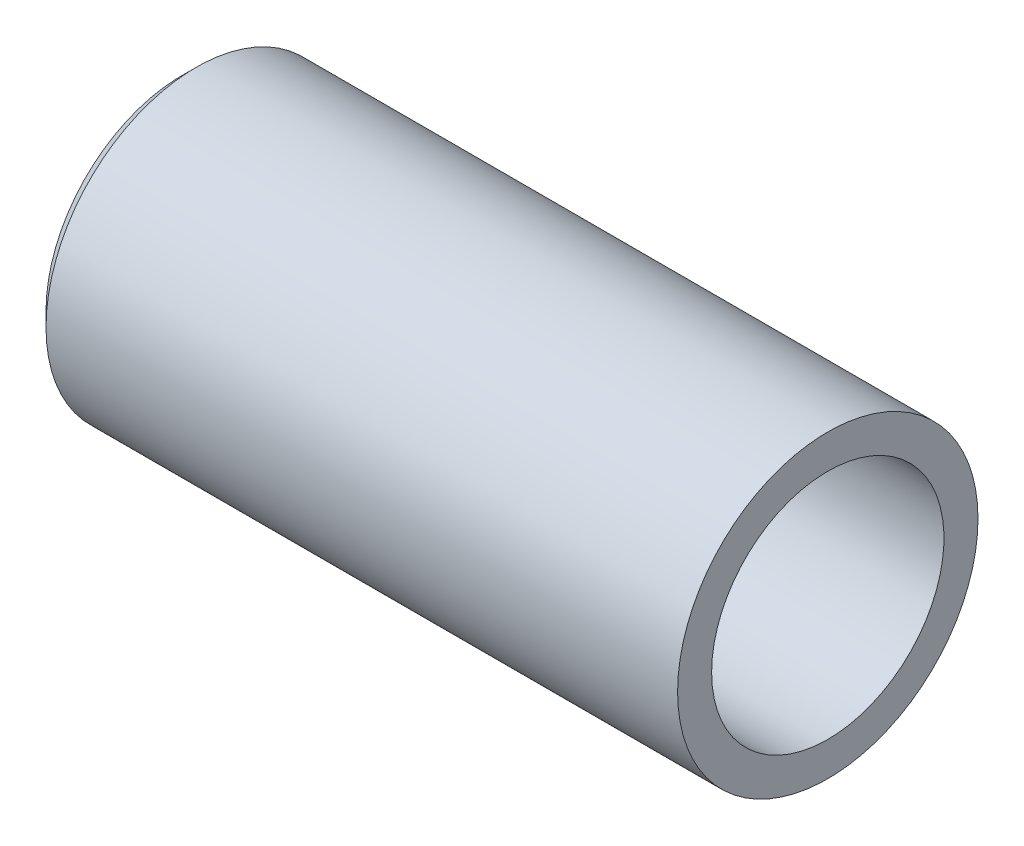
SolidWorks part; units mm, degrees
material "6061-T6 (SS)"
ref_plane "Front Plane" through (0, 0, 0) normal (0, 0, 1) x (1, 0, 0)
ref_plane "Top Plane" through (0, 0, 0) normal (0, 1, 0) x (1, 0, 0)
ref_plane "Right Plane" through (0, 0, 0) normal (1, 0, 0) x (0, 0, -1)
sketch "Sketch1" plane through (0, 0, 0) normal (0, 0, 1) x (1, 0, 0)
  line L0 (0, 0) -> (22.1407, 0) construction
  line L1 (0.8502, 5.2957) -> (23.1179, 5.2957)
  line L3 (0.3531, 4.0957) -> (23.1179, 4.0958)
  line L4 (23.3719, 5.2957) -> (23.3719, 1.3364) construction
  line L5 (23.1179, 5.2957) -> (23.1179, 4.0958)
  line L8 (0.3531, 4.0957) -> (0.3531, 4.7987)
  line L9 (0.3531, 4.7987) -> (0.8502, 5.2957)
  line L15 (0.3531, -7.9375) -> (0.3531, 7.9375) construction
  line L16 (23.3719, 12.0262) -> (23.3719, 15.8235) construction
  dimension "D4" = 45
  dimension "D2" = 1.2
  dimension "D3" = 0.254
  dimension "D1" = 8.1915
revolve "Revolve1" add sketch "Sketch1" angle 360 about L0
equation "\"D2@Sketch1\"=1.2mm"
equation "\"D1@Sketch1\"=5/16 + 0.01"
